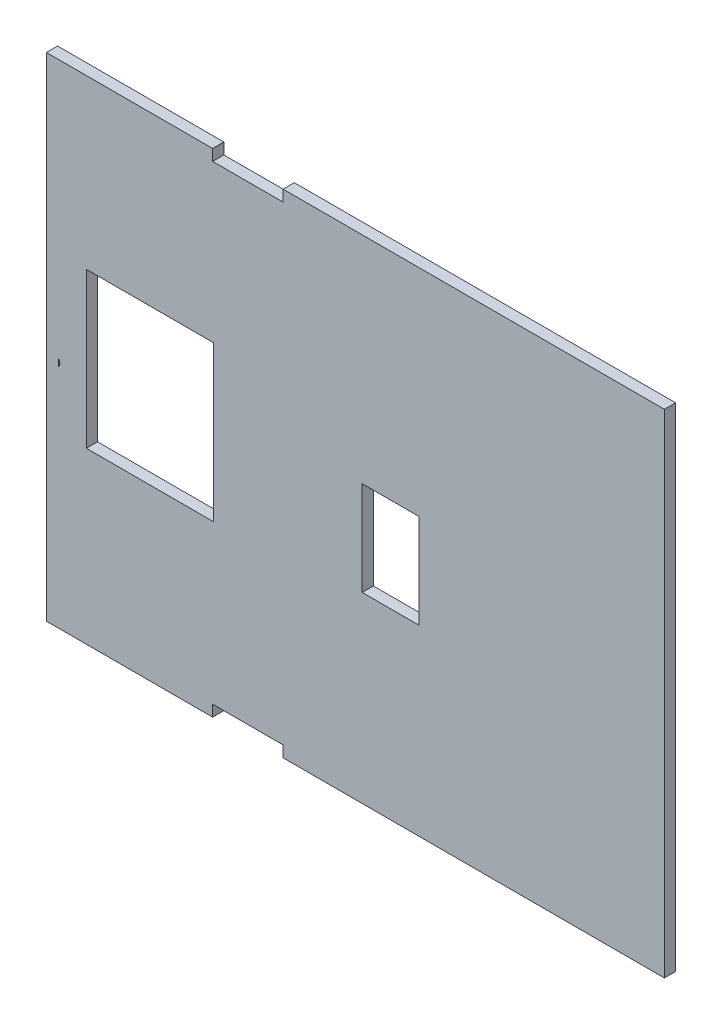
SolidWorks part; units mm, degrees
ref_plane "Front Plane" through (0, 0, 0) normal (0, 0, 1) x (1, 0, 0)
ref_plane "Top Plane" through (0, 0, 0) normal (0, 1, 0) x (1, 0, 0)
ref_plane "Right Plane" through (0, 0, 0) normal (1, 0, 0) x (0, 0, -1)
sketch "Sketch1" plane through (0, 0, 0) normal (0, 0, 1) x (1, 0, 0)
  line L1 (-87.5, 69.85) -> (87.5, 69.85)
  line L2 (-87.5, 69.85) -> (-87.5, -69.85)
  line L3 (-87.5, -69.85) -> (87.5, -69.85)
  line L4 (87.5, 69.85) -> (87.5, -69.85)
  line L5 (-87.5, 69.85) -> (87.5, -69.85) construction
  line L6 (-87.5, -69.85) -> (87.5, 69.85) construction
  point P0 (0, 0)
  dimension "D1" = 139.7
  dimension "D2" = 175
extrude "Boss-Extrude1" add sketch "Sketch1" along normal blind 3.18
sketch "Sketch2" plane through (0, 0, 3.18) normal (0, 0, 1) x (1, 0, 0)
  line L0 (0, 0) -> (87.5, 0) construction
  line L1 (-10, 69.85) -> (10, 69.85)
  line L2 (-10, 69.85) -> (-10, 66.67)
  line L3 (-10, 66.67) -> (-1.5, 66.67)
  line L4 (10, 69.85) -> (10, 66.67)
  line L5 (87.5, -69.85) -> (87.5, 69.85) construction
  line L6 (0, 0) -> (0, 69.85) construction
  line L7 (-1.5, 56.67) -> (1.5, 56.67)
  line L8 (-1.5, 56.67) -> (-1.5, 59.67)
  line L10 (1.5, 56.67) -> (1.5, 59.67)
  line L12 (87.5, 69.85) -> (-87.5, 69.85) construction
  line L13 (3.5, 62.67) -> (1.5, 62.67)
  line L14 (3.5, 62.67) -> (3.5, 59.67)
  line L15 (3.5, 59.67) -> (1.5, 59.67)
  line L16 (-3.5, 62.67) -> (-3.5, 59.67)
  line L17 (-10, -69.85) -> (-10, -66.67)
  line L18 (-10, -66.67) -> (-1.5, -66.67)
  line L19 (-1.5, -62.67) -> (-1.5, -66.67)
  line L20 (-1.5, -62.67) -> (-3.5, -62.67)
  line L21 (-3.5, -62.67) -> (-3.5, -59.67)
  line L22 (1.5, 66.67) -> (10, 66.67)
  line L23 (-1.5, 62.67) -> (-3.5, 62.67)
  line L24 (-1.5, -59.67) -> (-3.5, -59.67)
  line L25 (-1.5, -56.67) -> (-1.5, -59.67)
  line L26 (-1.5, -56.67) -> (1.5, -56.67)
  line L27 (-1.5, 59.67) -> (-3.5, 59.67)
  line L28 (1.5, -56.67) -> (1.5, -59.67)
  line L29 (-1.5, 62.67) -> (-1.5, 66.67)
  line L30 (1.5, 62.67) -> (1.5, 66.67)
  line L31 (3.5, -59.67) -> (1.5, -59.67)
  line L32 (3.5, -62.67) -> (3.5, -59.67)
  line L33 (3.5, -62.67) -> (1.5, -62.67)
  line L34 (1.5, -62.67) -> (1.5, -66.67)
  line L35 (1.5, -66.67) -> (10, -66.67)
  line L36 (10, -69.85) -> (10, -66.67)
  line L37 (-10, -69.85) -> (10, -69.85)
  line L38 (-87.5, 69.85) -> (-87.5, -69.85) construction
  line L39 (-87.5, 69.85) -> (-84.32, 69.85)
  line L40 (-87.5, 69.85) -> (-87.5, 9.875)
  line L41 (-87.5, 9.875) -> (-84.32, 9.875)
  line L42 (-84.32, 69.85) -> (-84.32, 9.875)
  line L43 (-87.5, -69.85) -> (-84.32, -69.85)
  line L44 (-87.5, -69.85) -> (-87.5, -9.875)
  line L45 (-87.5, -9.875) -> (-84.32, -9.875)
  line L46 (-84.32, -69.85) -> (-84.32, -9.875)
  line L47 (87.5, -9.875) -> (84.32, -9.875)
  line L48 (84.32, -69.85) -> (84.32, -9.875)
  line L49 (87.5, -69.85) -> (84.32, -69.85)
  line L50 (87.5, -69.85) -> (87.5, -9.875)
  line L51 (87.5, 9.875) -> (84.32, 9.875)
  line L52 (84.32, 69.85) -> (84.32, 9.875)
  line L53 (87.5, 69.85) -> (84.32, 69.85)
  line L54 (87.5, 69.85) -> (87.5, 9.875)
  line L70 (-28.8549, -66.67) -> (-20.3341, -66.67)
  line L71 (-40.3341, -69.85) -> (-20.3341, -69.85)
  line L72 (-40.3341, -69.85) -> (-40.3341, -66.67)
  line L73 (-40.3341, -66.67) -> (-31.8549, -66.67)
  line L74 (-20.3341, -69.85) -> (-20.3341, -66.67)
  line L75 (-31.8549, -62.67) -> (-33.773, -62.67)
  line L76 (-87.5, -69.85) -> (87.5, -69.85) construction
  line L77 (-31.8549, -56.85) -> (-28.8549, -56.85)
  line L78 (-31.8549, -56.85) -> (-31.8549, -59.67)
  line L80 (-28.8549, -56.85) -> (-28.8549, -59.67)
  line L83 (-26.773, -62.67) -> (-28.8549, -62.67)
  line L84 (-26.773, -62.67) -> (-26.773, -59.67)
  line L85 (-26.773, -59.67) -> (-28.8549, -59.67)
  line L86 (-33.773, -62.67) -> (-33.773, -59.67)
  line L91 (-31.8549, -59.67) -> (-33.773, -59.67)
  line L98 (-31.8549, -62.67) -> (-31.8549, -66.67)
  line L99 (-28.8549, -62.67) -> (-28.8549, -66.67)
  circle A0 centre (-85.5, 0) radius 1.5
  circle A1 centre (85.5, 0) radius 1.5
  point P0 (0, 50.5662)
  point P5 (0, 32.0079)
  point P10 (15.4931, 34.4893)
  point P67 (-32.11, -66.8097)
  point P72 (-32.3859, -61.3492)
  point P77 (-32.3859, -59.7197)
  dimension "D11" = 3
  dimension "D12" = 2
  dimension "D1" = 20
  dimension "D2" = 19.75
  dimension "D3" = 4
  dimension "D4" = 3
  dimension "D5" = 3.18
  dimension "D6" = 7
  dimension "D7" = 3
  dimension "D8" = 3
  dimension "D9" = 3.18
  dimension "D10" = 3.18
  dimension "D13" = 20
  dimension "D14" = 7
  dimension "D15" = 3.18
  dimension "D16" = 3
  dimension "D17" = 3
  dimension "D18" = 4
  dimension "D19" = 13
extrude "Cut-Extrude1" cut sketch "Sketch2" against normal through all
sketch "Sketch3" plane through (0, 0, 0) normal (0, 0, -1) x (-1, 0, 0)
  circle A0 centre (-35.6713, -47.9634) radius 1.59
  circle A1 centre (-35.6713, -30.7773) radius 1.59
extrude "Cut-Extrude2" cut sketch "Sketch3" against normal through all
sketch "Sketch4" plane through (0, 0, 0) normal (0, 0, -1) x (-1, 0, 0)
  circle A0 centre (-34.7507, 53.7803) radius 1.59
  circle A1 centre (-34.7507, 36.5942) radius 1.59
  circle A2 centre (36.2498, 53.7803) radius 1.59
  circle A3 centre (36.2498, 36.5942) radius 1.59
  circle A4 centre (35.9839, -30.7773) radius 1.59
  circle A5 centre (35.9839, -47.9634) radius 1.59
  circle A6 centre (-35.6713, -30.7773) radius 1.59
  circle A7 centre (-35.6713, -47.9634) radius 1.59
extrude "Cut-Extrude3" cut sketch "Sketch4" against normal through all
sketch "Sketch5" plane through (0, 0, 3.18) normal (0, 0, 1) x (1, 0, 0)
  line L1 (-46.5267, 67.382) -> (45.3995, 67.382)
  line L2 (-46.5267, 67.382) -> (-46.5267, -56.2746)
  line L3 (-46.5267, -56.2746) -> (45.3995, -56.2746)
  line L4 (45.3995, 67.382) -> (45.3995, -56.2746)
extrude "Boss-Extrude2" add sketch "Sketch5" against normal blind 3.18
sketch "Sketch6" plane through (0, 0, 0) normal (0, 0, -1) x (-1, 0, 0)
  line L1 (-26.8, -9.839) -> (-23.62, -9.839)
  line L2 (-26.8, -9.839) -> (-26.8, 9.911)
  line L3 (-26.8, 9.911) -> (-23.62, 9.911)
  line L4 (-23.62, -9.839) -> (-23.62, 9.911)
  line L5 (11.4836, -9.875) -> (14.6636, -9.875)
  line L6 (11.4836, -9.875) -> (11.4836, 9.875)
  line L7 (11.4836, 9.875) -> (14.6636, 9.875)
  line L8 (14.6636, -9.875) -> (14.6636, 9.875)
extrude "Cut-Extrude4" cut sketch "Sketch6" against normal through all
sketch "Sketch8" plane through (0, 0, 0) normal (0, 0, -1) x (-1, 0, 0)
  line L1 (10, -69.85) -> (-15.5604, -69.85)
  line L2 (10, -69.85) -> (10, -50.1707)
  line L3 (10, -50.1707) -> (-15.5604, -50.1707)
  line L4 (-15.5604, -69.85) -> (-15.5604, -50.1707)
extrude "Boss-Extrude3" add sketch "Sketch8" against normal blind 3.18
sketch "Sketch10" plane through (0, 0, 0) normal (0, 0, -1) x (-1, 0, 0)
  line L1 (-10, 67.382) -> (10, 67.382)
  line L2 (-10, 67.382) -> (-10, 69.85)
  line L3 (-10, 69.85) -> (10, 69.85)
  line L4 (10, 67.382) -> (10, 69.85)
extrude "Boss-Extrude4" add sketch "Sketch10" against normal blind 3.18
sketch "Sketch11" plane through (0, 0, 0) normal (0, 0, -1) x (-1, 0, 0)
  line L0 (-84.32, 69.85) -> (84.32, 69.85) construction
  line L1 (20.7931, 66.67) -> (29.4791, 66.67)
  line L2 (20.7931, 66.67) -> (20.7931, 69.85)
  line L3 (20.7931, 69.85) -> (40.7931, 69.85)
  line L4 (40.7931, 66.67) -> (40.7931, 69.85)
  line L6 (30.7931, 0) -> (0, 0) construction
  line L7 (29.4791, 62.67) -> (29.4791, 66.67)
  line L8 (29.4791, 56.85) -> (32.4791, 56.85)
  line L9 (29.4791, 56.85) -> (29.4791, 59.67)
  line L11 (32.4791, 56.85) -> (32.4791, 59.67)
  line L12 (32.4791, 66.67) -> (40.7931, 66.67)
  line L14 (27.2931, 59.67) -> (29.4791, 59.67)
  line L15 (27.2931, 59.67) -> (27.2931, 62.67)
  line L16 (27.2931, 62.67) -> (29.4791, 62.67)
  line L17 (34.2931, 59.67) -> (34.2931, 62.67)
  line L22 (30.7931, 56.85) -> (30.7931, 0) construction
  line L25 (32.4791, 62.67) -> (32.4791, 66.67)
  line L26 (32.4791, 59.67) -> (34.2931, 59.67)
  line L28 (32.4791, 62.67) -> (34.2931, 62.67)
  point P8 (30.4223, 62.891)
  point P11 (30.7931, 69.85)
  point P15 (30.4223, 62.1751)
  dimension "D1" = 20
  dimension "D2" = 3
  dimension "D3" = 3
  dimension "D4" = 13
  dimension "D5" = 7
  dimension "D6" = 4
extrude "Cut-Extrude5" cut sketch "Sketch11" against normal through all
sketch "Sketch12" plane through (0, 0, 0) normal (0, 0, -1) x (-1, 0, 0)
  line L1 (40.471, -17.0656) -> (76.4831, -17.0656)
  line L2 (40.471, -17.0656) -> (40.471, 26.8946)
  line L3 (40.471, 26.8946) -> (76.4831, 26.8946)
  line L4 (76.4831, -17.0656) -> (76.4831, 26.8946)
  line L5 (40.471, -17.0656) -> (76.4831, 26.8946) construction
  line L6 (40.471, 26.8946) -> (76.4831, -17.0656) construction
  point P0 (58.477, 4.9145)
extrude "Cut-Extrude6" cut sketch "Sketch12" against normal through all
sketch "Sketch13" plane through (0, 0, 0) normal (0, 0, -1) x (-1, 0, 0)
  line L1 (-17.9359, -13.3526) -> (-1.7618, -13.3526)
  line L2 (-17.9359, -13.3526) -> (-17.9359, 13.3526)
  line L3 (-17.9359, 13.3526) -> (-1.7618, 13.3526)
  line L4 (-1.7618, -13.3526) -> (-1.7618, 13.3526)
  line L5 (-17.9359, -13.3526) -> (-1.7618, 13.3526) construction
  line L6 (-17.9359, 13.3526) -> (-1.7618, -13.3526) construction
  point P0 (-9.8488, 0)
extrude "Cut-Extrude7" cut sketch "Sketch13" against normal through all
sketch "Sketch14" plane through (84.32, 0, 0) normal (1, 0, 0) x (0, 0, -1)
  line L1 (0, -69.85) -> (-3.18, -69.85)
  line L2 (0, -69.85) -> (0, 69.85)
  line L3 (0, 69.85) -> (-3.18, 69.85)
  line L4 (-3.18, -69.85) -> (-3.18, 69.85)
extrude "Boss-Extrude5" add sketch "Sketch14" along normal blind 3.18 and the other way blind 5
sketch "Sketch16" plane through (0, 0, 0) normal (0, 0, -1) x (-1, 0, 0)
  line L0 (20.3341, -69.85) -> (-87.5, -69.85) construction
  line L1 (-41.3018, -69.85) -> (-22.4174, -69.85)
  line L2 (-41.3018, -69.85) -> (-41.3018, 51.2062)
  line L3 (-41.3018, 51.2062) -> (-22.4174, 51.2062)
  line L4 (-22.4174, -69.85) -> (-22.4174, 51.2062)
  line L6 (6.6847, 15.8036) -> (17.5418, 15.8036)
  line L7 (6.6847, 15.8036) -> (6.6847, -19.634)
  line L8 (6.6847, -19.634) -> (17.5418, -19.634)
  line L9 (17.5418, 15.8036) -> (17.5418, -19.634)
  line L10 (17.5418, -69.85) -> (45.9706, -69.85)
  line L11 (17.5418, -69.85) -> (17.5418, -55.8486)
  line L12 (17.5418, -55.8486) -> (45.9706, -55.8486)
  line L13 (45.9706, -69.85) -> (45.9706, -55.8486)
  line L14 (20.7931, 69.85) -> (43.3701, 69.85)
  line L15 (20.7931, 69.85) -> (20.7931, 53.1205)
  line L16 (20.7931, 53.1205) -> (43.3701, 53.1205)
  line L17 (43.3701, 69.85) -> (43.3701, 53.1205)
extrude "Boss-Extrude6" add sketch "Sketch16" against normal blind 3.18
sketch "Sketch17" plane through (0, 0, 0) normal (0, 0, -1) x (-1, 0, 0)
  line L1 (-87.5, -69.85) -> (84.32, -69.85)
  line L2 (-87.5, -69.85) -> (-87.5, -75.025)
  line L3 (-87.5, -75.025) -> (84.32, -75.025)
  line L5 (84.32, 69.85) -> (-87.5, 69.85)
  line L7 (84.32, 74.4938) -> (-87.5, 74.4938)
  line L8 (-87.5, 69.85) -> (-87.5, 74.4938)
  line L10 (84.32, -69.85) -> (84.32, 69.85)
  line L11 (84.32, 74.4938) -> (87.8082, 74.4938)
  line L12 (87.8082, -69.85) -> (87.8082, 74.4938)
  line L13 (84.32, -75.025) -> (87.8082, -75.025)
  line L16 (87.8082, -75.025) -> (87.8082, -69.85)
extrude "Boss-Extrude7" add sketch "Sketch17" against normal blind 3.18
sketch "Sketch18" plane through (0, 0, 3.18) normal (0, 0, 1) x (1, 0, 0)
  line L0 (-87.8082, -75.025) -> (-87.8082, 74.4938) construction
  line L1 (87.5, -75.025) -> (-87.8082, -75.025)
  line L2 (87.5, -75.025) -> (87.5, -65.2062)
  line L3 (87.5, -65.2062) -> (-87.8082, -65.2062)
  line L4 (-87.8082, -75.025) -> (-87.8082, -65.2062)
extrude "Cut-Extrude8" cut sketch "Sketch18" against normal blind 3.18
sketch "Sketch19" plane through (0, 0, 0) normal (0, 0, -1) x (-1, 0, 0)
  line L0 (-87.5, -65.2062) -> (87.8082, -65.2062) construction
  line L1 (40.6582, -62.0262) -> (20.6582, -62.0262)
  line L2 (40.6582, -62.0262) -> (40.6582, -65.2062)
  line L3 (40.6582, -65.2062) -> (20.6582, -65.2062)
  line L4 (20.6582, -62.0262) -> (20.6582, -65.2062)
  line L5 (87.8082, 74.4938) -> (-87.5, 74.4938) construction
  line L6 (40.6582, 71.3138) -> (20.6582, 71.3138)
  line L7 (40.6582, 71.3138) -> (40.6582, 74.4938)
  line L8 (40.6582, 74.4938) -> (20.6582, 74.4938)
  line L9 (20.6582, 71.3138) -> (20.6582, 74.4938)
extrude "Cut-Extrude9" cut sketch "Sketch19" against normal blind 5
